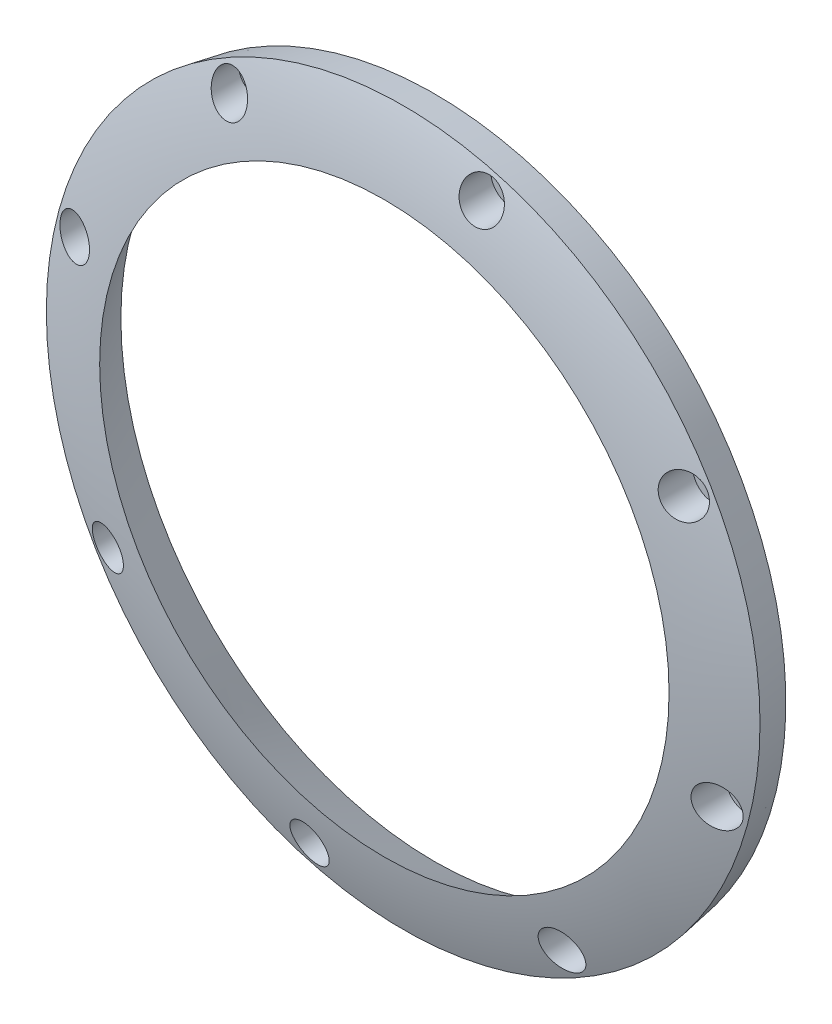
SolidWorks part; units mm, degrees
material "PUR"
ref_plane "Front Plane" through (0, 0, 0) normal (0, 0, 1) x (1, 0, 0)
ref_plane "Top Plane" through (0, 0, 0) normal (0, 1, 0) x (1, 0, 0)
ref_plane "Right Plane" through (0, 0, 0) normal (1, 0, 0) x (0, 0, -1)
sketch "Sketch1" plane through (0, 0, 0) normal (0, 0, 1) x (1, 0, 0)
  circle A0 centre (0, 0) radius 100 construction
  circle A1 centre (0, 0) radius 100
  circle A2 centre (0, 0) radius 112
  arc A3 (111.914, 4.3889) -> (-77.2845, 81.0624) centre (0, 0) ccw construction
sketch "Sketch2" plane through (0, 0, 0) normal (0, 1, 0) x (1, 0, 0)
  line L0 (-112, 0) -> (112, 0) construction
  line L1 (-100, 0) -> (100, 0) construction
  line L2 (-112, 0) -> (112, 0) construction
  line L3 (-100, 0) -> (100, 0) construction
  line L4 (-100, 0) -> (-112, 0)
  line L5 (-100, 0) -> (-90.7624, -16)
  line L6 (0, 0) -> (0, -16) construction
  line L7 (-112, 0) -> (-113.7633, -10)
  line L8 (-90.7624, -16) -> (0, -16) construction
  line L9 (-90.7624, -16) -> (-100, -10) construction
  line L10 (-100, -10) -> (-113.7633, -10) construction
  line L11 (-100, -10) -> (-100, 0) construction
  line L12 (-90.7624, -16) -> (-76.2049, -18.5669) construction
  line L13 (-112, 0) -> (-112, -10) construction
  arc A0 (-90.7624, -16) -> (-113.7633, -10) centre (-65.1412, 129.305) cw
  dimension "D1" = 60
  dimension "D2" = 10
  dimension "D3" = 16
  dimension "D4" = 10
  dimension "D5" = 10
revolve "Revolve1" add sketch "Sketch2" angle 360 about L6
sketch "Sketch3" plane through (0, 0, 0) normal (0, 0, -1) x (-1, 0, 0)
  circle A0 centre (-102.3881, -27.4348) radius 2.65 construction
  circle A1 centre (-102.3881, -27.4348) radius 2.65
extrude "Cut-Extrude1" cut sketch "Sketch3" against normal through all
sketch "Sketch4" plane through (0, 0, 0) normal (0, 0, -1) x (-1, 0, 0)
  circle A0 centre (-102.3881, -27.4348) radius 6.5
  dimension "D1" = 13
extrude "Cut-Extrude2" cut sketch "Sketch4" against normal through all from offset 3 offset against normal yes
pattern_circular "CirPattern1" count 8 over 360 about axis through (0, 0, 0) along (0, 0, -1) of "Cut-Extrude1", "Cut-Extrude2"
